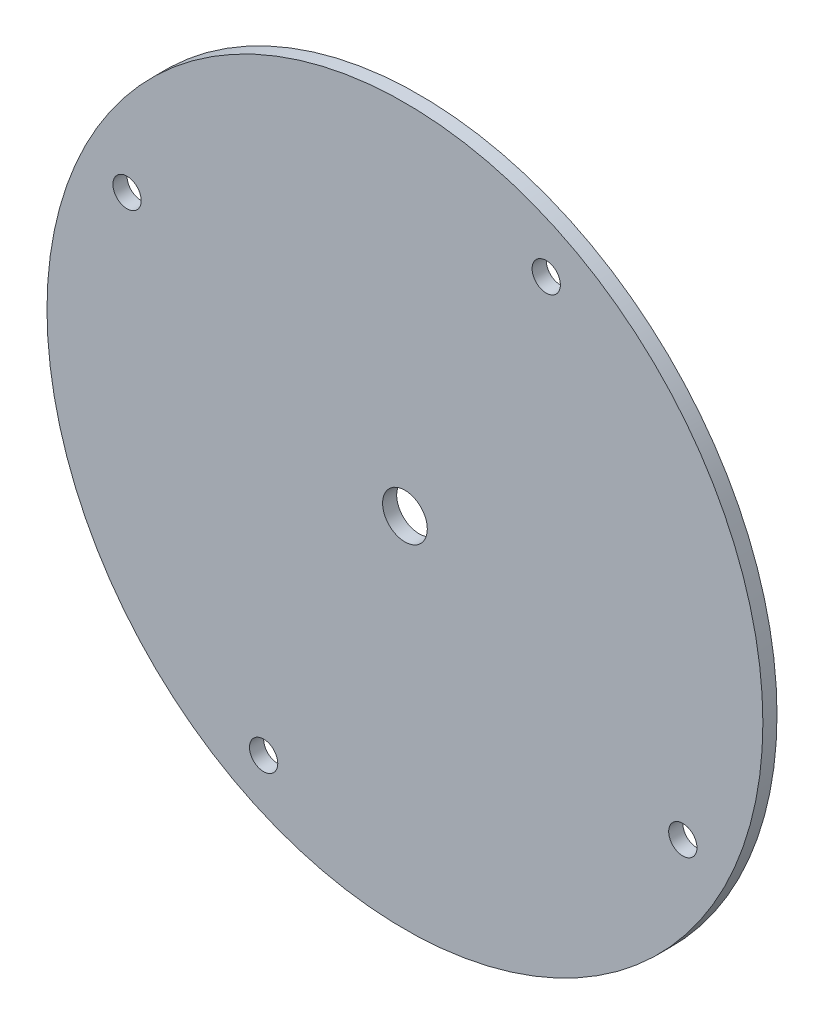
SolidWorks part; units mm, degrees
material "1060 Alloy"
ref_plane "Front Plane" through (0, 0, 0) normal (0, 0, 1) x (1, 0, 0)
ref_plane "Top Plane" through (0, 0, 0) normal (0, 1, 0) x (1, 0, 0)
ref_plane "Right Plane" through (0, 0, 0) normal (1, 0, 0) x (0, 0, -1)
sketch "Sketch1" plane through (0, 0, 0) normal (0, 0, 1) x (1, 0, 0)
  line L5 (50, -50) -> (-50, 50) construction
  line L6 (50, 50) -> (-50, -50) construction
  line L31 (24.5, 59) -> (27.25, 54.2369)
  line L32 (27.25, 54.2369) -> (32.75, 54.2369)
  line L33 (32.75, 54.2369) -> (35.5, 59)
  line L36 (-38.9, 50) -> (38.9, 50) construction
  line L50 (0, -76) -> (0, 122.6166) construction
  line L51 (-76, 0) -> (103.3867, 0) construction
  line L52 (35.5, 59) -> (32.75, 63.7631)
  line L53 (32.75, 63.7631) -> (27.25, 63.7631)
  line L54 (27.25, 63.7631) -> (24.5, 59)
  line L55 (-59, 24.5) -> (-54.2369, 27.25)
  line L56 (-54.2369, 27.25) -> (-54.2369, 32.75)
  line L57 (-54.2369, 32.75) -> (-59, 35.5)
  line L58 (-59, 35.5) -> (-63.7631, 32.75)
  line L59 (-63.7631, 32.75) -> (-63.7631, 27.25)
  line L60 (-63.7631, 27.25) -> (-59, 24.5)
  line L61 (59, -24.5) -> (54.2369, -27.25)
  line L62 (54.2369, -27.25) -> (54.2369, -32.75)
  line L96 (54.2369, -32.75) -> (59, -35.5)
  line L97 (59, -35.5) -> (63.7631, -32.75)
  line L98 (63.7631, -32.75) -> (63.7631, -27.25)
  line L99 (63.7631, -27.25) -> (59, -24.5)
  line L100 (-24.5, -59) -> (-27.25, -54.2369)
  line L101 (-27.25, -54.2369) -> (-32.75, -54.2369)
  line L102 (-32.75, -54.2369) -> (-35.5, -59)
  line L103 (-35.5, -59) -> (-32.75, -63.7631)
  line L104 (-32.75, -63.7631) -> (-27.25, -63.7631)
  line L105 (-27.25, -63.7631) -> (-24.5, -59)
  arc A0 (0, 76) -> (-72.0169, -24.281) centre (0, 0) ccw
  circle A1 centre (30, 59) radius 3
  arc A2 (76, 0) -> (0, 76) centre (0, 0) ccw
  arc A3 (-72.0169, -24.281) -> (0, -76) centre (0, 0) ccw
  arc A4 (0, -76) -> (76, 0) centre (0, 0) ccw
  circle A5 centre (59, -30) radius 3
  circle A6 centre (-30, -59) radius 3
  circle A7 centre (-59, 30) radius 3
  circle A8 centre (30, 59) radius 5.5 construction
  circle A9 centre (-59, 30) radius 5.5 construction
  circle A10 centre (59, -30) radius 5.5 construction
  circle A11 centre (-30, -59) radius 5.5 construction
  dimension "D1" = 152
  dimension "D9" = 30
  dimension "D2" = 59
  dimension "D15" = 11
  dimension "D16" = 11
  dimension "D17" = 11
  dimension "D3" = 30
  dimension "D4" = 59
  dimension "D5" = 59
  dimension "D6" = 59
  dimension "D10" = 30
  dimension "D11" = 30
extrude "Boss-Extrude3" add sketch "Sketch1" along normal blind 3 contours A4 A2 A0 A3 L105 L104 L103 L102 L101 L100 L99 L98 L97 L96 L62 L61 L60 L59 L58 L57 L56 L55 L54 L53 L52 L33 L32 L31 | L59 L60 L55 L56 L57 L58 A7 | L53 L54 L31 L32 L33 L52 A1 | L98 L99 L61 L62 L96 L97 A5 | L104 L105 L100 L101 L102 L103 A6 region at (26.001, 61.3088, 0) region at (-61.3088, 26.001, 0) region at (61.3088, -26.001, 0) region at (-26.001, -61.3088, 0) region at (0, 0, 0)
sketch "Sketch2" plane through (0, 0, 3) normal (0, 0, 1) x (1, 0, 0)
  circle A0 centre (0, 0) radius 4.75
  dimension "D1" = 9.5
extrude "Cut-Extrude1" cut sketch "Sketch2" against normal through all
